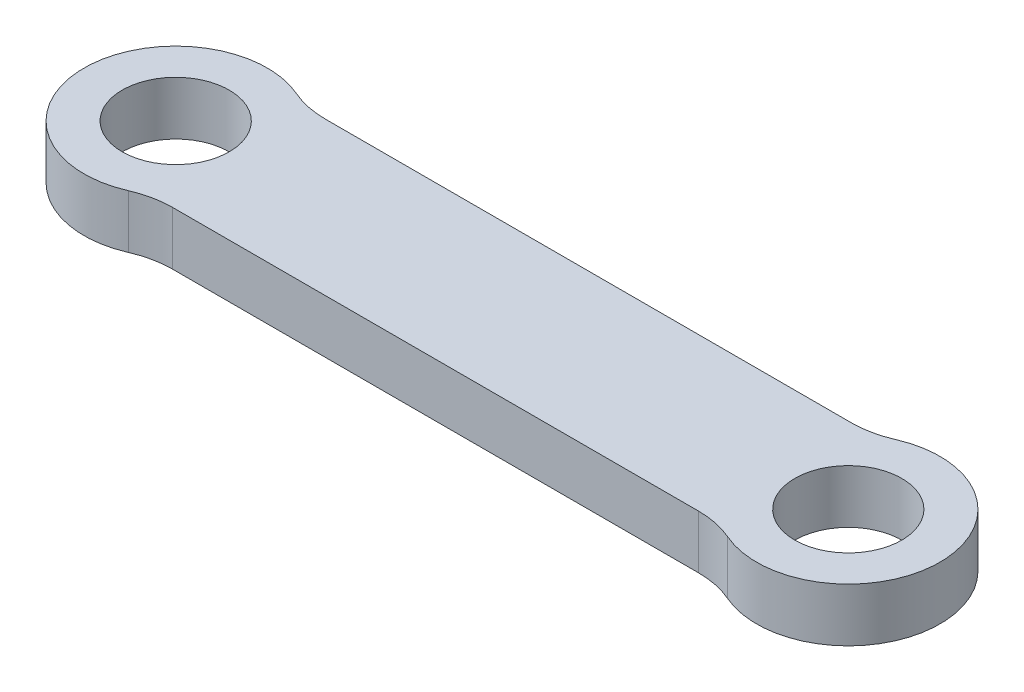
SolidWorks part; units mm, degrees
ref_plane "Front Plane" through (0, 0, 0) normal (0, 0, 1) x (1, 0, 0)
ref_plane "Top Plane" through (0, 0, 0) normal (0, 1, 0) x (1, 0, 0)
ref_plane "Right Plane" through (0, 0, 0) normal (1, 0, 0) x (0, 0, -1)
sketch "Sketch1" plane through (0, 0, 0) normal (0, 1, 0) x (1, 0, 0)
  line L0 (0, 0) -> (22, 0) construction
  line L1 (1.6583, 2.5) -> (20.3417, 2.5)
  line L2 (1.6583, -2.5) -> (20.3417, -2.5)
  circle A0 centre (0, 0) radius 3
  circle A1 centre (22, 0) radius 3
  circle A2 centre (0, 0) radius 1.75
  circle A3 centre (22, 0) radius 1.75
  dimension "D1" = 6
  dimension "D3" = 6
  dimension "D5" = 3.5
  dimension "D6" = 3.5
  dimension "D2" = 22
  dimension "D4" = 2.5
extrude "Boss-Extrude1" add sketch "Sketch1" along normal blind 1.75 contours A2 A0 | L0 A0 L2 A1 | A0 L0 A1 L1 | A1 A3 region at (2.5686, 0, 1.3785) region at (11, 0, -1.2811) region at (11, 0, 1.2811) region at (19.4314, 0, -1.3785)
fillet "Fillet1" radius 3 4 edges at (1.6583, 0.875, 2.5) (20.3417, 0.875, 2.5) (20.3417, 0.875, -2.5) (1.6583, 0.875, -2.5)
